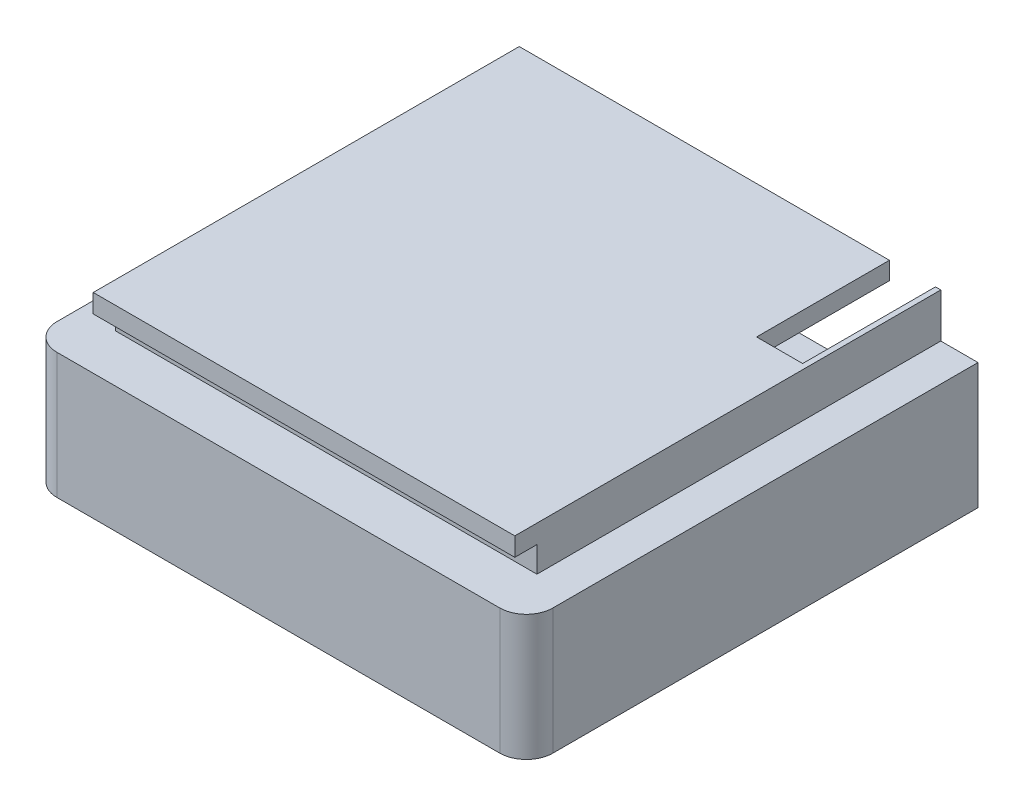
SolidWorks part; units mm, degrees
ref_plane "Front Plane" through (0, 0, 0) normal (0, 0, 1) x (1, 0, 0)
ref_plane "Top Plane" through (0, 0, 0) normal (0, 1, 0) x (1, 0, 0)
ref_plane "Right Plane" through (0, 0, 0) normal (1, 0, 0) x (0, 0, -1)
sketch "Sketch1" plane through (0, 0, 0) normal (0, 1, 0) x (1, 0, 0)
  line L0 (0, 51) -> (5, 51)
  line L1 (0, 0) -> (56, 0)
  line L2 (0, 0) -> (0, 51)
  line L4 (56, 0) -> (56, 51)
  line L6 (5, 7) -> (51, 7)
  line L7 (51, 7) -> (51, 51)
  line L8 (51, 51) -> (56, 51)
  line L9 (5, 51) -> (5, 49)
  line L10 (5, 49) -> (5, 7)
  dimension "D1" = 51
  dimension "D2" = 56
  dimension "D3" = 42
  dimension "D4" = 46
  dimension "D5" = 5
  dimension "D6" = 2
extrude "Boss-Extrude8" add sketch "Sketch1" along normal blind 10.2
sketch "Sketch8" plane through (0, 10.2, 0) normal (0, 1, 0) x (1, 0, 0)
  line L1 (0, 51) -> (56, 51)
  line L2 (0, 51) -> (0, 0)
  line L3 (0, 0) -> (56, 0)
  line L4 (56, 51) -> (56, 0)
extrude "Boss-Extrude9" add sketch "Sketch8" along normal blind 2
sketch "Sketch10" plane through (0, 0, 0) normal (-1, 0, 0) x (0, 0, 1)
  line L0 (0, 12.2) -> (-2.5, 12.2)
  line L1 (-51, 12.2) -> (0, 12.2) construction
  line L2 (-2.5, 12.2) -> (-2.5, 9.7)
  line L3 (-2.5, 9.7) -> (-5, 9.7)
  line L4 (-5, 9.7) -> (-5, 7.2)
  line L5 (-5, 7.2) -> (0, 7.2)
  line L6 (0, 12.2) -> (0, 0) construction
  line L7 (0, 7.2) -> (0, 12.2)
  dimension "D1" = 2.5
  dimension "D2" = 2.5
  dimension "D3" = 2.5
  dimension "D4" = 2.5
extrude "Cut-Extrude1" cut sketch "Sketch10" against normal offset from surface (48 mm away) 4 from offset 4 up to face at (56, 6.1, -25.5) offset against normal yes
sketch "Sketch12" plane through (0, 12.2, 0) normal (0, 1, 0) x (1, 0, 0)
  line L1 (0, 51) -> (4, 51)
  line L2 (0, 51) -> (0, 0)
  line L3 (0, 0) -> (4, 0)
  line L4 (4, 51) -> (4, 0)
  line L5 (52, 0) -> (56, 0)
  line L6 (52, 0) -> (52, 51)
  line L7 (52, 51) -> (56, 51)
  line L8 (56, 0) -> (56, 51)
extrude "Cut-Extrude2" cut sketch "Sketch12" against normal up to surface (5 mm away) up to face at (28, 7.2, -2.5)
sketch "Sketch11" plane through (0, 0, 0) normal (0, 0, 1) x (1, 0, 0)
  line L0 (0, -4.5) -> (56, -4.5)
  line L1 (0, 0) -> (56, 0)
  line L2 (0, 0) -> (0, -7)
  line L3 (0, -7) -> (56, -7)
  line L4 (56, 0) -> (56, -7)
  line L5 (0, -2) -> (56, -2)
  line M9 (0, 0) -> (56, 0)
  dimension "D1" = 2
  dimension "D2" = 2.5
  dimension "D3" = 2.5
extrude "Boss-Extrude10" add sketch "Sketch11" against normal up to surface (51 mm away) contours L2 L5 L4 M9 region at (28, -1, 0) up to face at (28, 6.1333, -51)
extrude "Boss-Extrude11" add sketch "Sketch11<3>" against normal blind 2.5 contours L5 L2 L0 L4 region at (28, -3.25, 0)
sketch "Sketch11<3>" plane through (0, 0, 0) normal (0, 0, 1) x (1, 0, 0) same geometry as "Sketch11"
extrude "Boss-Extrude12" add sketch "Sketch11<4>" against normal blind 5 contours L4 L0 L2 L3 region at (28, -5.75, 0)
sketch "Sketch11<4>" plane through (0, 0, 0) normal (0, 0, 1) x (1, 0, 0) same geometry as "Sketch11"
sketch "Sketch13" plane through (0, -2, 0) normal (0, -1, 0) x (1, 0, 0)
  line L0 (56, -51) -> (0, -51) construction
  line L1 (0, -2.5) -> (5, -2.5)
  line L2 (0, -2.5) -> (0, -51)
  line L3 (0, -51) -> (5, -51)
  line L4 (5, -2.5) -> (5, -51)
  line L6 (56, -2.5) -> (51, -2.5)
  line L7 (56, -2.5) -> (56, -51)
  line L8 (56, -51) -> (51, -51)
  line L9 (51, -2.5) -> (51, -51)
  dimension "D1" = 5
extrude "Boss-Extrude13" add sketch "Sketch13" along normal up to surface (5 mm away) up to face at (28, -7, -2.5)
sketch "Sketch14" plane through (0, 0, -51) normal (0, 0, -1) x (-1, 0, 0)
  line L0 (-52, 12.2) -> (-4, 12.2) construction
  line L1 (-51, 12.2) -> (-46, 12.2)
  line L2 (-51, 12.2) -> (-51, -2)
  line L3 (-51, -2) -> (-46, -2)
  line L4 (-46, 12.2) -> (-46, -2)
  line L5 (-51, -2) -> (-5, -2) construction
  line L6 (-51, 10.2) -> (-51, 0) construction
  line L13 (-51, 0) -> (-5, 0) construction
  line L14 (-5, -7) -> (-10, -7)
  line L15 (-5, -7) -> (-5, 0)
  line L16 (-5, 0) -> (-10, 0)
  line L17 (-10, -7) -> (-10, 0)
  dimension "D1" = 5
extrude "Cut-Extrude3" cut sketch "Sketch14" against normal blind 15
fillet "Fillet1" radius 3 2 edges at (56, 0.1, 0) (0, 0.1, 0)
other "Move Face1" flip direction yes face at (28, 9.7, -3.75) face at (28, 10.95, -2.5) face at (28, 8.45, -5) face at (28, -2, -31.375) offset 0.2 parameters "D1"=0.2
other "Move Face2" flip direction yes face at (28, 9.9, -3.95) face at (28, 8.55, -5.2) face at (28, 11.05, -2.7) face at (52, 9.7667, -19.6333) face at (4, 9.7667, -19.6333) offset 0.2 parameters "D1"=0.2
other "Move Face3" flip direction yes face at (5, -0.62, -20.3) face at (51, 1.5167, -22.9167) face at (28, -5.75, -5) face at (28, -4.5, -3.75) face at (28, -3.15, -2.5) face at (28, -1.8, -31.375) offset 0.2 parameters "D1"=0.2
equation "\"Wall_Thickness\"= 5mm"
